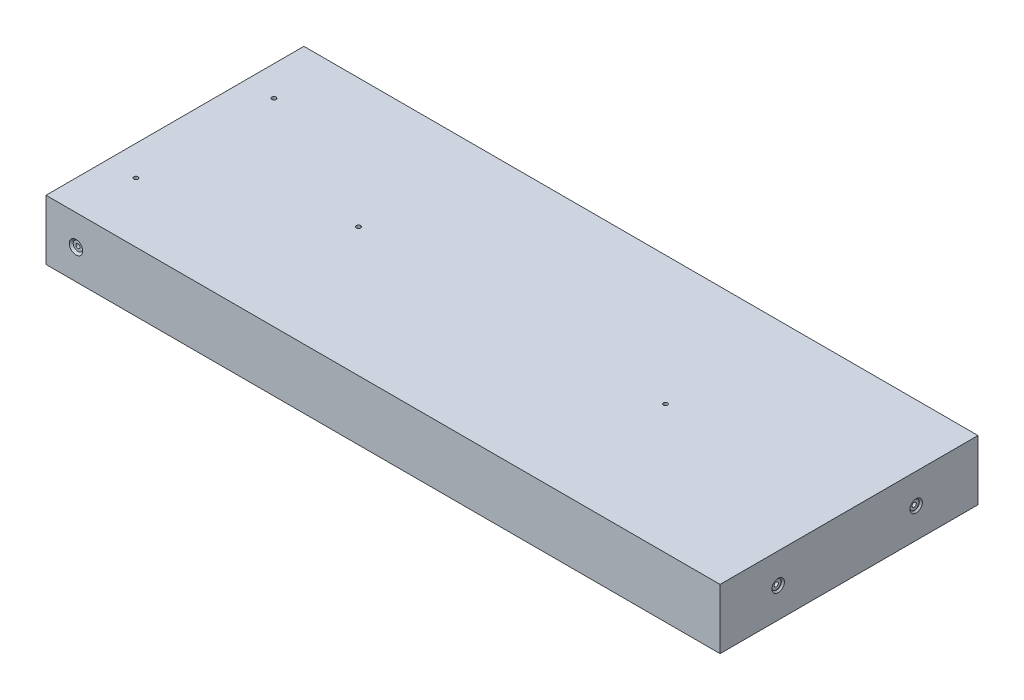
SolidWorks part; units mm, degrees
ref_plane "Front Plane" through (0, 0, 0) normal (0, 0, 1) x (1, 0, 0)
ref_plane "Top Plane" through (0, 0, 0) normal (0, 1, 0) x (1, 0, 0)
ref_plane "Right Plane" through (0, 0, 0) normal (1, 0, 0) x (0, 0, -1)
sketch "Sketch1" plane through (0, 0, 0) normal (0, 1, 0) x (1, 0, 0)
  line L1 (-142.7, 54.6) -> (142.7, 54.6)
  line L2 (-142.7, 54.6) -> (-142.7, -54.6)
  line L3 (-142.7, -54.6) -> (142.7, -54.6)
  line L4 (142.7, 54.6) -> (142.7, -54.6)
  line L5 (-142.7, 54.6) -> (142.7, -54.6) construction
  line L6 (-142.7, -54.6) -> (142.7, 54.6) construction
  point P0 (0, 0)
  dimension "D1" = 109.2
  dimension "D2" = 285.4
extrude "Boss-Extrude1" add sketch "Sketch1" along normal blind 25.4
hole_wizard "CBORE for #0 Binding Head Machine Screw1" positions "Sketch2" profile "Sketch3" counterbore size "#0" standard "ANSI Inch"
sketch "Sketch2" plane through (0, 0, 54.6) normal (0, 0, 1) x (1, 0, 0)
  line L0 (-142.7, 25.4) -> (-142.7, 0) construction
  line L1 (-142.7, 25.4) -> (142.7, 25.4) construction
  point P0 (-130, 12.7)
  dimension "D1" = 12.7
  dimension "D2" = 12.7
sketch "Sketch3" plane through (-130, 12.7, 54.6) normal (1, 0, 0) x (0, -1, 0)
  line L0 (0, 0) -> (0, 30.5342)
  line L1 (0, 30.5342) -> (0.889, 30)
  line L2 (0.889, 30) -> (0.889, 0.8128)
  line L3 (0.889, 0.8128) -> (1.985, 0.8128)
  line L5 (1.985, 0.8128) -> (1.985, 0.8725)
  line L6 (1.985, 0.8725) -> (2.8575, 0)
  line L7 (2.8575, 0) -> (0, 0)
  line L8 (-1.985, 0.8725) -> (-2.8575, 0) construction
  line L10 (0, 30.5342) -> (-0.889, 30) construction
  line L11 (0, -6.35) -> (0, 107.95) construction
  dimension "Hole Dia." = 1.778
  dimension "Hole Depth" = 30
  dimension "C'Bore Dia." = 3.97
  dimension "C'Bore Depth" = 0.8128
  dimension "Near C'Sink Dia." = 5.715
  dimension "Near C'Sink Angle" = 90
  dimension "Drill Angle" = 118
mirror "Mirror1" about plane through (0, 0, 0) normal (0, 0, 1) of "CBORE for #0 Binding Head Machine Screw1"
hole_wizard "CBORE for #0 Binding Head Machine Screw2" positions "Sketch4" profile "Sketch5" counterbore size "#0" standard "ANSI Inch"
sketch "Sketch4" plane through (142.7, 0, 0) normal (1, 0, 0) x (0, 0, -1)
  line L0 (-54.6, 25.4) -> (-54.6, 0) construction
  line L2 (-54.6, 25.4) -> (54.6, 25.4) construction
  point P0 (-30, 12.7)
  point P2 (28.4, 12.7)
  dimension "D1" = 58.4
  dimension "D2" = 24.6
  dimension "D4" = 12.7
sketch "Sketch5" plane through (142.7, 12.7, 30) normal (0, 1, 0) x (0, 0, -1)
  line L0 (0, 0) -> (0, 30.5342)
  line L1 (0, 30.5342) -> (0.889, 30)
  line L2 (0.889, 30) -> (0.889, 0.8128)
  line L3 (0.889, 0.8128) -> (1.985, 0.8128)
  line L5 (1.985, 0.8128) -> (1.985, 0.635)
  line L6 (1.985, 0.635) -> (2.62, 0)
  line L7 (2.62, 0) -> (0, 0)
  line L8 (-1.985, 0.635) -> (-2.62, 0) construction
  line L10 (0, 30.5342) -> (-0.889, 30) construction
  line L11 (0, -6.35) -> (0, 107.95) construction
  dimension "Hole Dia." = 1.778
  dimension "Hole Depth" = 30
  dimension "C'Bore Dia." = 3.97
  dimension "C'Bore Depth" = 0.8128
  dimension "Near C'Sink Dia." = 5.24
  dimension "Near C'Sink Angle" = 90
  dimension "Drill Angle" = 118
hole_wizard "CBORE for #0 Binding Head Machine Screw4" positions "Sketch8" profile "Sketch9" counterbore size "#0" standard "ANSI Inch"
sketch "Sketch8" plane through (0, 0, 0) normal (0, -1, 0) x (-1, 0, 0)
  line L0 (0, 54.6) -> (0, -54.6) construction
  line L1 (-142.7, 54.6) -> (142.7, 54.6) construction
  line L2 (142.7, -54.6) -> (-142.7, -54.6) construction
  line L4 (142.7, 0) -> (-142.7, 0) construction
  line L5 (142.7, 54.6) -> (142.7, -54.6) construction
  line L6 (-142.7, -54.6) -> (-142.7, 54.6) construction
  point P0 (65, 0)
  point P2 (-65, 0)
  dimension "D1" = 130
sketch "Sketch9" plane through (-65, 0, 0) normal (1, 0, 0) x (0, 0, -1)
  line L0 (0, 0) -> (0, 30.5342)
  line L1 (0, 30.5342) -> (0.889, 30)
  line L2 (0.889, 30) -> (0.889, 0.8128)
  line L3 (0.889, 0.8128) -> (1.985, 0.8128)
  line L5 (1.985, 0.8128) -> (1.985, 0.8725)
  line L6 (1.985, 0.8725) -> (2.8575, 0)
  line L7 (2.8575, 0) -> (0, 0)
  line L8 (-1.985, 0.8725) -> (-2.8575, 0) construction
  line L10 (0, 30.5342) -> (-0.889, 30) construction
  line L11 (0, -6.35) -> (0, 107.95) construction
  dimension "Hole Dia." = 1.778
  dimension "Hole Depth" = 30
  dimension "C'Bore Dia." = 3.97
  dimension "C'Bore Depth" = 0.8128
  dimension "Near C'Sink Dia." = 5.715
  dimension "Near C'Sink Angle" = 90
  dimension "Drill Angle" = 118
hole_wizard "CBORE for #0 Binding Head Machine Screw6" positions "Sketch12" profile "Sketch13" counterbore size "#0" standard "ANSI Inch" end condition through all
sketch "Sketch12" plane through (0, 0, 0) normal (0, -1, 0) x (-1, 0, 0)
  line L0 (142.7, 54.6) -> (142.7, -54.6) construction
  line L1 (-142.7, 54.6) -> (142.7, 54.6) construction
  point P0 (130, 29.2)
  point P2 (130, -29.2)
  dimension "D1" = 12.7
  dimension "D2" = 12.7
  dimension "D3" = 58.4
  dimension "D4" = 25.4
sketch "Sketch13" plane through (-130, 0, -29.2) normal (1, 0, 0) x (0, 0, -1)
  line L0 (0, 0) -> (0, 25.4)
  line L1 (0, 25.4) -> (0.889, 25.4)
  line L3 (0.889, 25.4) -> (0.889, 0.8128)
  line L4 (1.985, 0.8128) -> (0.889, 0.8128)
  line L5 (1.985, 0.8128) -> (1.985, 0.8725)
  line L6 (1.985, 0.8725) -> (2.8575, 0)
  line L7 (2.8575, 0) -> (0, 0)
  line L8 (-1.985, 0.8725) -> (-2.8575, 0) construction
  line L11 (0, -6.35) -> (0, 107.95) construction
  dimension "Thru Hole Dia." = 1.778
  dimension "Thru Hole Depth" = 25.4
  dimension "C'Bore Dia." = 3.97
  dimension "C'Bore Depth" = 0.8128
  dimension "Near C'Sink Dia." = 5.715
  dimension "Near C'Sink Angle" = 90
